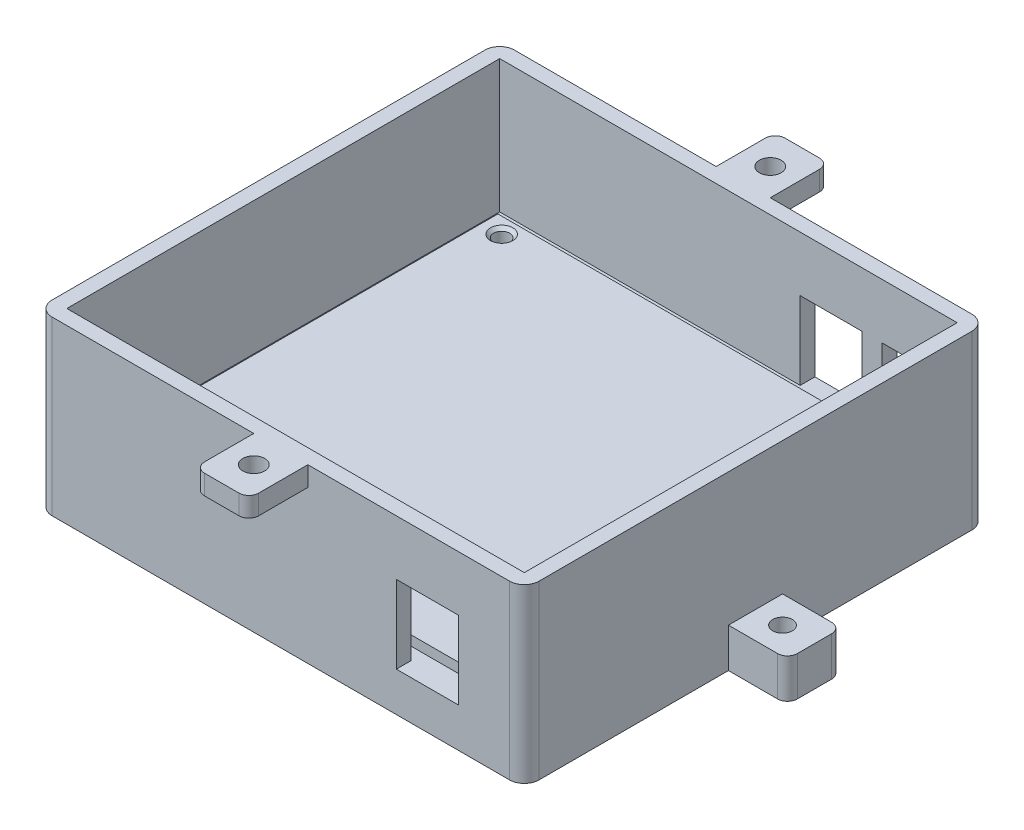
SolidWorks part; units mm, degrees
ref_plane "Plano frontal" through (0, 0, 0) normal (0, 0, 1) x (1, 0, 0)
ref_plane "Plano superior" through (0, 0, 0) normal (0, 1, 0) x (1, 0, 0)
ref_plane "Plano direito" through (0, 0, 0) normal (1, 0, 0) x (0, 0, -1)
sketch "Esboço1" plane through (0, 0, 0) normal (0, 1, 0) x (1, 0, 0)
  line L0 (0, -3) -> (93, -3)
  line L1 (0, 0) -> (93, 0)
  line L2 (0, 0) -> (0, 88)
  line L3 (0, 88) -> (93, 88)
  line L4 (93, 0) -> (93, 88)
  line L5 (-3, 0) -> (-3, 88)
  line L6 (0, 91) -> (93, 91)
  line L7 (96, 0) -> (96, 88)
  line L9 (-3, 38.5) -> (-13, 38.5)
  line L10 (-3, 38.5) -> (-3, 49.5)
  line L11 (-3, 49.5) -> (-13, 49.5)
  line L12 (-15, 40.5) -> (-15, 47.5)
  line L13 (46.5, 88) -> (46.5, 0) construction
  line L15 (0, 44) -> (93, 44) construction
  line L20 (0, 0) -> (93, 88) construction
  line L21 (96, 49.5) -> (106, 49.5)
  line L22 (108, 40.5) -> (108, 47.5)
  line L23 (96, 38.5) -> (106, 38.5)
  line L24 (96, 38.5) -> (96, 49.5)
  arc A3 (93, -3) -> (96, 0) centre (93, 0) ccw
  arc A4 (93, 91) -> (96, 88) centre (93, 88) cw
  arc A5 (-3, 88) -> (0, 91) centre (0, 88) cw
  arc A6 (0, -3) -> (-3, 0) centre (0, 0) cw
  arc A7 (-13, 38.5) -> (-15, 40.5) centre (-13, 40.5) cw
  arc A8 (-13, 49.5) -> (-15, 47.5) centre (-13, 47.5) ccw
  circle A9 centre (-8.5, 44) radius 2
  circle A13 centre (101.5, 44) radius 2
  arc A14 (106, 49.5) -> (108, 47.5) centre (106, 47.5) cw
  arc A15 (106, 38.5) -> (108, 40.5) centre (106, 40.5) ccw
  point P15 (96, -3)
  point P24 (96, 91)
  dimension "D10" = 2
  dimension "D7" = 38.5
  dimension "D8" = 3
  dimension "D11" = 10
  dimension "D1" = 93
  dimension "D2" = 88
  dimension "D3" = 99
  dimension "D4" = 94
  dimension "D5" = 3
  dimension "D6" = 3
  dimension "D9" = 38.5
  dimension "D12" = 5.5
  dimension "D13" = 5.5
extrude "Ressalto-extrusão2" add sketch "Esboço1" along normal blind 35 contours L0 L7 L6 L5 L4 L1 L2 L3 region at (-1.156, 0, 1.156)
extrude "Ressalto-extrusão3" add sketch "Esboço1<5>" along normal blind 8 contours L1 L4 L3 L2 region at (46.5, 0, -44)
sketch "Esboço1<5>" plane through (0, 0, 0) normal (0, 1, 0) x (1, 0, 0) same geometry as "Esboço1"
extrude "Ressalto-extrusão6" add sketch "Esboço1<7>" along normal blind 8 contours L11 A8 L12 A7 L9 L5 A9 | L23 A15 L22 A14 L21 L7 A13 region at (-8, 0, -38.6628) region at (96.1628, 0, -44)
sketch "Esboço1<7>" plane through (0, 0, 0) normal (0, 1, 0) x (1, 0, 0) same geometry as "Esboço1"
sketch "Esboço4" plane through (0, 35, 0) normal (0, 1, 0) x (1, 0, 0)
  line L0 (0, -3) -> (93, -3) construction
  line L1 (41, -3) -> (52, -3)
  line L2 (41, -3) -> (41, -13)
  line L3 (43, -15) -> (50, -15)
  line L4 (52, -3) -> (52, -13)
  line L6 (0, 44) -> (93, 44) construction
  line L7 (0, 0) -> (0, 88) construction
  line L8 (93, 0) -> (93, 88) construction
  line L9 (43, 103) -> (50, 103)
  line L10 (52, 91) -> (52, 101)
  line L11 (41, 91) -> (52, 91)
  line L12 (41, 91) -> (41, 101)
  arc A0 (50, -15) -> (52, -13) centre (50, -13) ccw
  arc A1 (41, -13) -> (43, -15) centre (43, -13) ccw
  circle A2 centre (46.5, -8.5) radius 2.2186
  circle A3 centre (46.5, 96.5) radius 2.2186
  arc A4 (50, 103) -> (52, 101) centre (50, 101) cw
  arc A5 (41, 101) -> (43, 103) centre (43, 101) cw
  dimension "D3" = 2
  dimension "D1" = 41
  dimension "D2" = 41
  dimension "D4" = 10
  dimension "D5" = 5.5
  dimension "D6" = 5.5
extrude "Ressalto-extrusão7" add sketch "Esboço4" against normal blind 4
sketch "Esboço5" plane through (0, 8, 0) normal (0, 1, 0) x (1, 0, 0)
  line L0 (0, 0) -> (0, 88) construction
  line L1 (2.175, 85.46) -> (90.825, 85.46)
  line L2 (2.175, 85.46) -> (2.175, 2.54)
  line L3 (2.175, 2.54) -> (90.825, 2.54)
  line L4 (90.825, 85.46) -> (90.825, 2.54)
  line L5 (93, 0) -> (93, 88) construction
  line L6 (0, 88) -> (93, 88) construction
  line L7 (0, 0) -> (93, 0) construction
  dimension "D1" = 2.175
  dimension "D2" = 2.175
  dimension "D3" = 2.54
  dimension "D4" = 2.54
extrude "Ressalto-extrusão8" add sketch "Esboço5" along normal blind 2
sketch "Esboço7" plane through (0, 0, -88) normal (0, 0, 1) x (1, 0, 0)
  line L0 (90.825, 8) -> (2.175, 8) construction
  line L1 (61.08, 23.81) -> (73.68, 23.81)
  line L2 (61.08, 23.81) -> (61.08, 8)
  line L3 (61.08, 8) -> (73.68, 8)
  line L4 (73.68, 23.81) -> (73.68, 8)
  line L5 (0, 35) -> (0, 0) construction
  line L9 (0, 35) -> (93, 35) construction
  line L10 (77.72, 23.81) -> (90.32, 23.81)
  line L11 (77.72, 23.81) -> (77.72, 8)
  line L12 (77.72, 8) -> (90.32, 8)
  line L13 (90.32, 23.81) -> (90.32, 8)
  line L14 (0, 8) -> (93, 8) construction
  dimension "D1" = 61.08
  dimension "D2" = 12.6
  dimension "D3" = 15.81
  dimension "D4" = 11.19
  dimension "D5" = 4.04
  dimension "D6" = 0
  dimension "D7" = 0
extrude "Corte-extrusão1" cut sketch "Esboço7" against normal through all
sketch "Esboço8" plane through (0, 0, 0) normal (0, 0, -1) x (-1, 0, 0)
  line L0 (-2.175, 8) -> (-90.825, 8) construction
  line L1 (-82.59, 23.81) -> (-69.99, 23.81)
  line L2 (-82.59, 23.81) -> (-82.59, 8)
  line L3 (-82.59, 8) -> (-69.99, 8)
  line L4 (-69.99, 23.81) -> (-69.99, 8)
  line L5 (-93, 35) -> (-93, 8) construction
  line L8 (0, 35) -> (-93, 35) construction
  dimension "D1" = 10.41
  dimension "D2" = 11.19
  dimension "D3" = 15.81
  dimension "D4" = 12.6
extrude "Corte-extrusão2" cut sketch "Esboço8" against normal through all
sketch "Esboço9" plane through (0, 10, 0) normal (0, 1, 0) x (1, 0, 0)
  line L0 (0, 0) -> (0, 88) construction
  line L3 (0, 88) -> (61.08, 88) construction
  line L5 (0, 0) -> (69.99, 0) construction
  line L6 (93, 0) -> (93, 88) construction
  line L7 (82.59, 0) -> (93, 0) construction
  circle A0 centre (6.12, 82.28) radius 2
  circle A1 centre (6.12, 5.83) radius 2
  circle A2 centre (86.89, 5.83) radius 2
  dimension "D1" = 6.12
  dimension "D2" = 5.72
  dimension "D3" = 6.12
  dimension "D4" = 5.83
  dimension "D5" = 6.11
  dimension "D6" = 5.83
hole_wizard "Furo com folga de #41" positions "3DSketch1" profile "Esboço10" hole size "#4" standard "Ansi Inch"
sketch3d "3DSketch1"
  point P0 (6.12, 10, -82.28)
  point P3 (6.12, 10, -5.83)
  point P6 (86.89, 10, -5.83)
sketch "Esboço10" plane through (6.12, 10, -82.28) normal (1, 0, 0) x (0, 0, 1)
  line L0 (0, 0) -> (0, 8.9806)
  line L1 (0, 8.9806) -> (1.6319, 8)
  line L2 (1.6319, 8) -> (1.6319, 0.635)
  line L3 (1.6319, 0.635) -> (2.2669, 0)
  line L5 (2.2669, 0) -> (0, 0)
  line L6 (-1.6319, 0.635) -> (-2.2669, 0) construction
  line L10 (0, 8.9806) -> (-1.632, 8) construction
  line L11 (0, -6.35) -> (0, 107.95) construction
  dimension "Hole Dia." = 3.2639
  dimension "Hole Depth" = 8
  dimension "Near C'Sink Dia." = 4.5339
  dimension "Near C'Sink Angle" = 90
  dimension "Drill Angle" = 118
